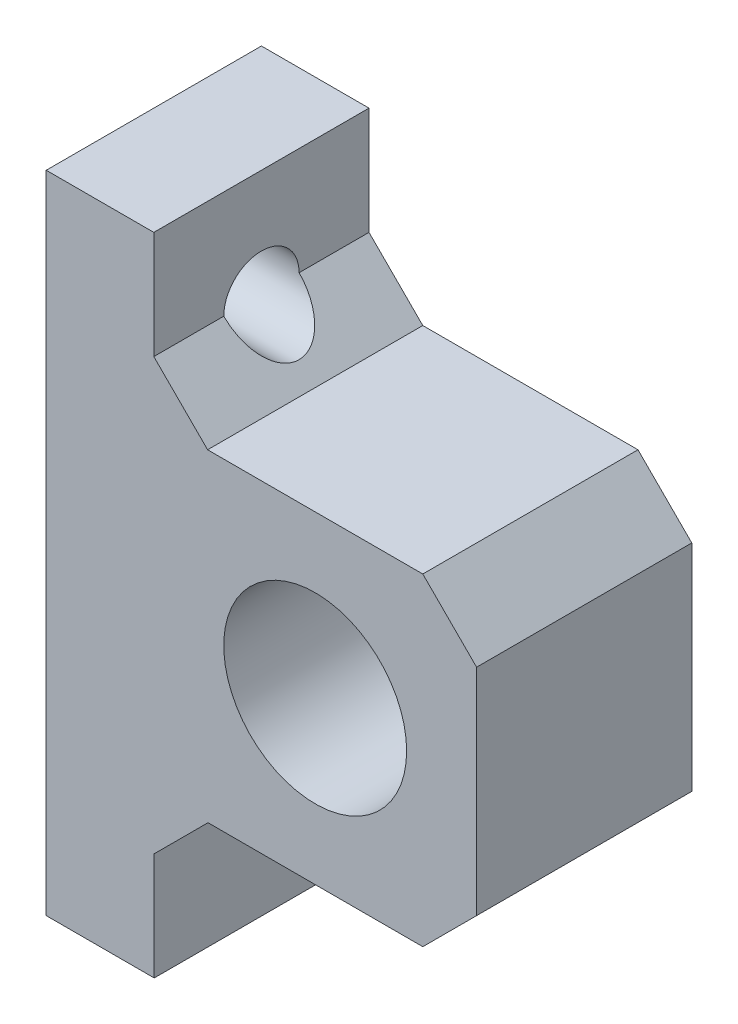
SolidWorks part; units mm, degrees
ref_plane "Front Plane" through (0, 0, 0) normal (0, 0, 1) x (1, 0, 0)
ref_plane "Top Plane" through (0, 0, 0) normal (0, 1, 0) x (1, 0, 0)
ref_plane "Right Plane" through (0, 0, 0) normal (1, 0, 0) x (0, 0, -1)
sketch "Sketch1" plane through (0, 0, 0) normal (0, 0, 1) x (1, 0, 0)
  line L0 (3.6965, -34.4358) -> (3.6965, -19.4358)
  line L1 (-6.3408, 25.5642) -> (3.6592, 25.5642)
  line L2 (-6.3408, 25.5642) -> (-6.3408, -34.4358)
  line L3 (-6.3408, -34.4358) -> (3.6965, -34.4358)
  line L4 (3.6592, 25.5642) -> (3.6592, 10.5642)
  line L5 (3.6592, 10.5642) -> (33.6592, 10.5642)
  line L7 (3.6965, -19.4358) -> (33.6592, -19.4358)
  line L8 (33.6592, 10.5642) -> (33.6592, -19.4358)
  circle A0 centre (18.6592, -4.4358) radius 8.5
  point P11 (3.6592, 10.3001)
  dimension "D8" = 17
  dimension "D1" = 60
  dimension "D2" = 10
  dimension "D3" = 30
  dimension "D4" = 30
  dimension "D5" = 15
  dimension "D6" = 40
  dimension "D7" = 15
extrude "Boss-Extrude1" add sketch "Sketch1" along normal blind 20
chamfer "Chamfer1" distance 5 angle 45 4 edges at (3.6965, -19.4358, 10) (33.6592, -19.4358, 10) (33.6592, 10.5642, 10) (3.6592, 10.5642, 10)
sketch "Sketch2" plane through (-6.3408, 0, 0) normal (-1, 0, 0) x (0, 0, 1)
  line L0 (20, 25.5642) -> (0, 25.5642) construction
  line L1 (20, 25.5642) -> (20, -34.4358) construction
  circle A0 centre (10, 15.5642) radius 3.5
  point P6 (2.2317, 6.155)
  dimension "D3" = 7
  dimension "D1" = 10
  dimension "D2" = 10
extrude "Cut-Extrude1" cut sketch "Sketch2" against normal blind 20
pattern_linear "LPattern1" count 200 spacing 40 along (0, -1, 0) of "Cut-Extrude1"
